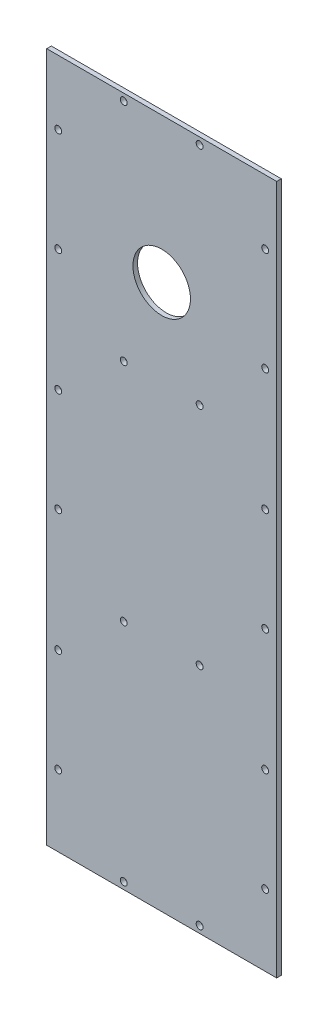
SolidWorks part; units mm, degrees
material "Alumina"
ref_plane "Front Plane" through (0, 0, 0) normal (0, 0, 1) x (1, 0, 0)
ref_plane "Top Plane" through (0, 0, 0) normal (0, 1, 0) x (1, 0, 0)
ref_plane "Right Plane" through (0, 0, 0) normal (1, 0, 0) x (0, 0, -1)
sketch "Sketch1" plane through (0, 0, 0) normal (0, 0, 1) x (1, 0, 0)
  line L1 (50, -150) -> (-50, -150)
  line L2 (50, -150) -> (50, 150)
  line L3 (50, 150) -> (-50, 150)
  line L4 (-50, -150) -> (-50, 150)
  line L5 (50, -150) -> (-50, 150) construction
  line L6 (50, 150) -> (-50, -150) construction
  point P0 (0, 0)
  dimension "D1" = 100
  dimension "D2" = 300
extrude "Boss-Extrude1" add sketch "Sketch1" along normal blind 2
sketch "Sketch2" plane through (0, 0, 2) normal (0, 0, 1) x (1, 0, 0)
  line L0 (-50, 150) -> (-50, -150) construction
  line L1 (50, 150) -> (-50, 150) construction
  line L2 (-50, -150) -> (50, -150) construction
  line L4 (0, -55) -> (0, 55) construction
  circle A0 centre (-45, 122) radius 1.5
  circle A1 centre (-45, 77) radius 1.5
  circle A2 centre (45, 122) radius 1.5
  circle A3 centre (45, 77) radius 1.5
  circle A4 centre (-45, 24) radius 1.5
  circle A5 centre (-45, -21) radius 1.5
  circle A6 centre (45, 24) radius 1.5
  circle A7 centre (45, -21) radius 1.5
  circle A8 centre (-45, -74) radius 1.5
  circle A9 centre (-45, -119) radius 1.5
  circle A10 centre (45, -74) radius 1.5
  circle A11 centre (45, -119) radius 1.5
  circle A13 centre (16.5, -147) radius 1.5
  circle A14 centre (-16.5, -147) radius 1.5
  circle A15 centre (-16.5, -49) radius 1.5
  circle A16 centre (16.5, -49) radius 1.5
  circle A17 centre (-16.5, 49) radius 1.5
  circle A18 centre (16.5, 49) radius 1.5
  circle A19 centre (-16.5, 147) radius 1.5
  circle A20 centre (16.5, 147) radius 1.5
  dimension "D1" = 3
  dimension "D3" = 28
  dimension "D4" = 3
  dimension "D6" = 5
  dimension "D10" = 3
  dimension "D11" = 33
  dimension "D13" = 3
  dimension "D2" = 5
  dimension "D5" = 45
  dimension "D9" = 31
  dimension "D7" = 2
  dimension "D8" = 3
  dimension "D12" = 4
extrude "Cut-Extrude1" cut sketch "Sketch2" against normal blind 10
sketch "Sketch3" plane through (0, 0, 0) normal (0, 0, -1) x (-1, 0, 0)
  line L0 (-50, 150) -> (50, 150) construction
  line L1 (-50, -150) -> (-50, 150) construction
  circle A0 centre (0, 87) radius 12.5
  dimension "D2" = 25
  dimension "D3" = 50
  dimension "D1" = 63
extrude "Cut-Extrude2" cut sketch "Sketch3" against normal blind 10
